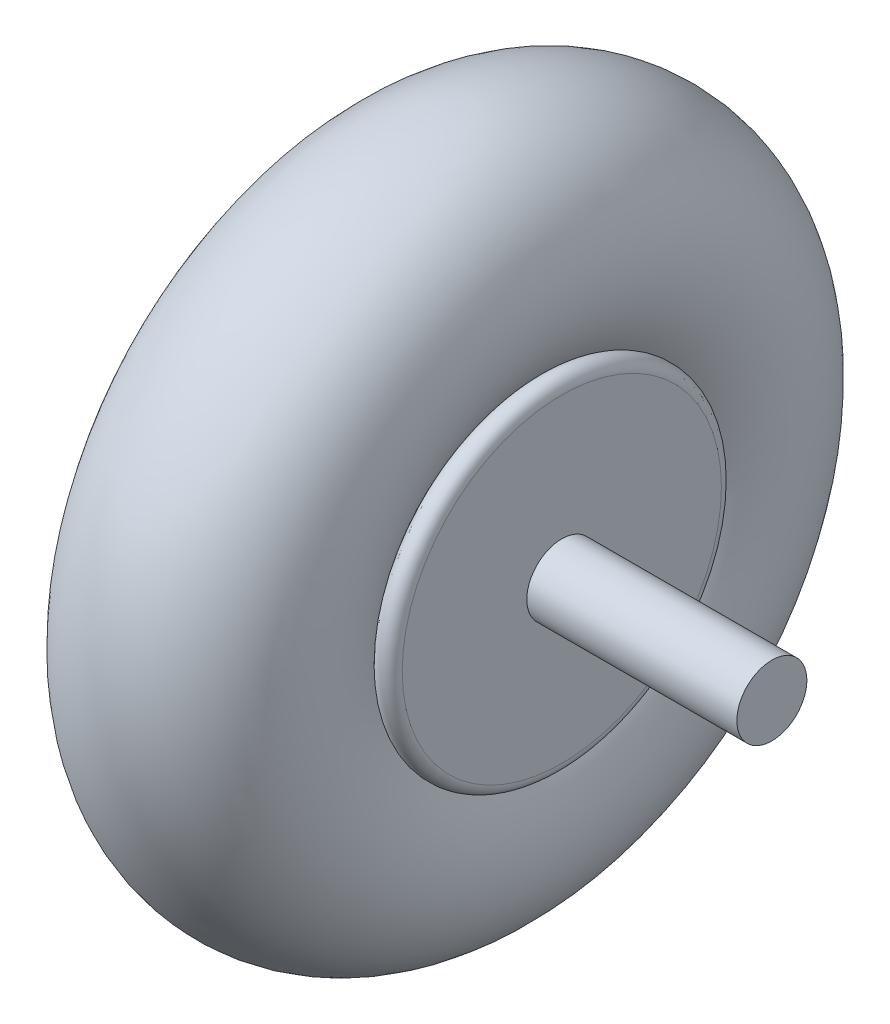
SolidWorks part; units mm, degrees
ref_plane "前视基准面" through (0, 0, 0) normal (0, 0, 1) x (1, 0, 0)
ref_plane "上视基准面" through (0, 0, 0) normal (0, 1, 0) x (1, 0, 0)
ref_plane "右视基准面" through (0, 0, 0) normal (1, 0, 0) x (0, 0, -1)
sketch "草图5" plane through (0, 0, 0) normal (0, 0, 1) x (1, 0, 0)
  line L1 (-6, 5) -> (6, 5)
  line L2 (-6, 5) -> (-6, -5)
  line L3 (-6, -5) -> (6, -5)
  line L4 (6, 5) -> (6, -5)
extrude "凸台-拉伸3" add sketch "草图5" along normal blind 1
ref_plane "基准面1" through (0, 0, 0) normal (1, 0, 0) x (0, 0, -1)
ref_plane "基准面2" through (0, 0, 0) normal (0, 0, 1) x (1, 0, 0)
sketch "草图6" plane through (0, 0, 0) normal (0, 0, 1) x (1, 0, 0)
  circle A0 centre (0, 20) radius 10
sketch "草图7" plane through (0, 0, 0) normal (1, 0, 0) x (0, 0, -1)
  circle A0 centre (0, 0) radius 20
sketch "草图9" plane through (0, 0, 0) normal (0, 0, -1) x (-1, 0, 0)
  line L0 (10, 20) -> (10, 0)
  line L2 (-10, 20) -> (-10, 0)
  line L3 (-10, 0) -> (10, 0)
  arc A0 (-10, 20) -> (10, 20) centre (0, 20) ccw
revolve "旋转1" add sketch "草图9" angle 360 about L3
fillet "圆角2" radius 1 2 edges at (-10, 0, -20) (10, 0, -20)
sweep "扫描3" add profiles "草图6" path "草图7"
sketch "草图10" plane through (10, 0, 0) normal (1, 0, 0) x (0, 0, -1)
  circle A0 centre (0, 0) radius 3
extrude "凸台-拉伸6" add sketch "草图10" along normal blind 18 separate body contours A0
combine bodies "组合1" operation type add bodies to combine 114 110
sketch "草图11" plane through (-10, 0, 0) normal (-1, 0, 0) x (0, 0, 1)
  circle A0 centre (0, 0) radius 3
extrude "凸台-拉伸7" add sketch "草图11" along normal blind 8 separate body
combine bodies "组合2" operation type add bodies to combine 116 115
